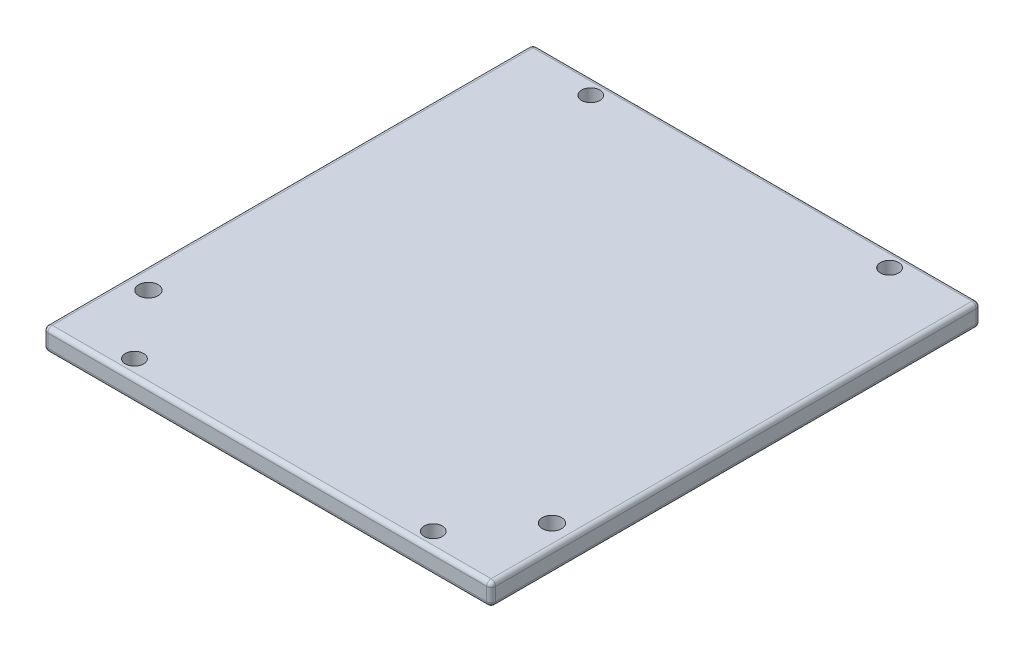
SolidWorks part; units mm, degrees
ref_plane "Front Plane" through (0, 0, 0) normal (0, 0, 1) x (1, 0, 0)
ref_plane "Top Plane" through (0, 0, 0) normal (0, 1, 0) x (1, 0, 0)
ref_plane "Right Plane" through (0, 0, 0) normal (1, 0, 0) x (0, 0, -1)
sketch "Sketch1" plane through (0, 0, 0) normal (0, 1, 0) x (1, 0, 0)
  line L0 (40.5, 88.55) -> (40.5, 0) construction
  line L1 (0, 0) -> (81, 0)
  line L2 (0, 0) -> (0, 88.55)
  line L3 (0, 88.55) -> (81, 88.55)
  line L4 (81, 0) -> (81, 88.55)
  circle A0 centre (4, 15) radius 1.75
  circle A1 centre (13.475, 3) radius 1.65
  circle A2 centre (13.475, 85.55) radius 1.65
  circle A3 centre (77, 15) radius 1.75
  circle A4 centre (67.525, 3) radius 1.65
  circle A5 centre (67.525, 85.55) radius 1.65
  point P12 (4, 15)
  dimension "D3" = 4
  dimension "D4" = 13.475
  dimension "D5" = 3
  dimension "D6" = 3
  dimension "D7" = 15
  dimension "D8" = 3.3
  dimension "D9" = 3.3
  dimension "D10" = 3.5
  dimension "D11" = 13.475
  dimension "D1" = 81
  dimension "D2" = 88.55
extrude "Boss-Extrude1" add sketch "Sketch1" along normal blind 4
fillet "Fillet3" radius 0.8 12 edges at (0, 2, -88.55) (0, 4, -44.275) (0, 0, -44.275) (0, 2, 0) (40.5, 4, 0) (40.5, 0, 0) (81, 2, 0) (81, 4, -44.275) (81, 0, -44.275) (81, 2, -88.55) (40.5, 4, -88.55) (40.5, 0, -88.55)
sketch "Sketch2" plane through (0, 0, 0) normal (0, -1, 0) x (1, 0, 0)
  line L1 (10.75, -25.5) -> (15.75, -25.5)
  line L2 (10.75, -25.5) -> (10.75, -45.5)
  line L3 (10.75, -45.5) -> (15.75, -45.5)
  line L4 (15.75, -25.5) -> (15.75, -45.5)
  circle A1 centre (4, -15) radius 1.75 construction
  dimension "D3" = 10.5
  dimension "D1" = 6.75
  dimension "D2" = 20
  dimension "D4" = 5
extrude "Boss-Extrude2" add sketch "Sketch2" along normal blind 8.8
sketch "Sketch5" plane through (0, 0, -45.5) normal (0, 0, -1) x (-1, 0, 0)
  line L0 (-15.75, -8.8) -> (-15.75, 0) construction
  line L1 (-10.75, 0) -> (-13.95, 0)
  line L2 (-10.75, 0) -> (-10.75, -6.8)
  line L3 (-10.75, -6.8) -> (-13.95, -6.8)
  line L4 (-13.95, 0) -> (-13.95, -6.8)
  dimension "D1" = 6.8
  dimension "D2" = 1.8
extrude "Cut-Extrude1" cut sketch "Sketch5" against normal through all
fillet "Fillet1" radius 3 1 edges at (15.75, 0, -35.5) second distance 5 first distance on face at (13.475, 0, -1.35)
fillet "Fillet2" radius 0.5 9 edges at (13.25, -8.8, -25.5) (13.25, -8.8, -45.5) (10.75, -7.8, -25.5) (10.75, -7.8, -45.5) (10.75, -6.8, -35.5) (13.95, -3.4, -45.5) (13.95, -3.4, -25.5) (10.75, -8.8, -35.5) (15.75, -8.8, -35.5)
ref_axis "Axis1" through (40.5, 0, -0.8) along (0, 0, -1)
ref_plane "Plane1" through (40.5, 0, 0) normal (-1, 0, 0) x (0, 0, -1)
mirror "Mirror1" about plane through (40.5, 0, 0) normal (-1, 0, 0) of "Fillet2", "Fillet1", "Cut-Extrude1", "Boss-Extrude2"
